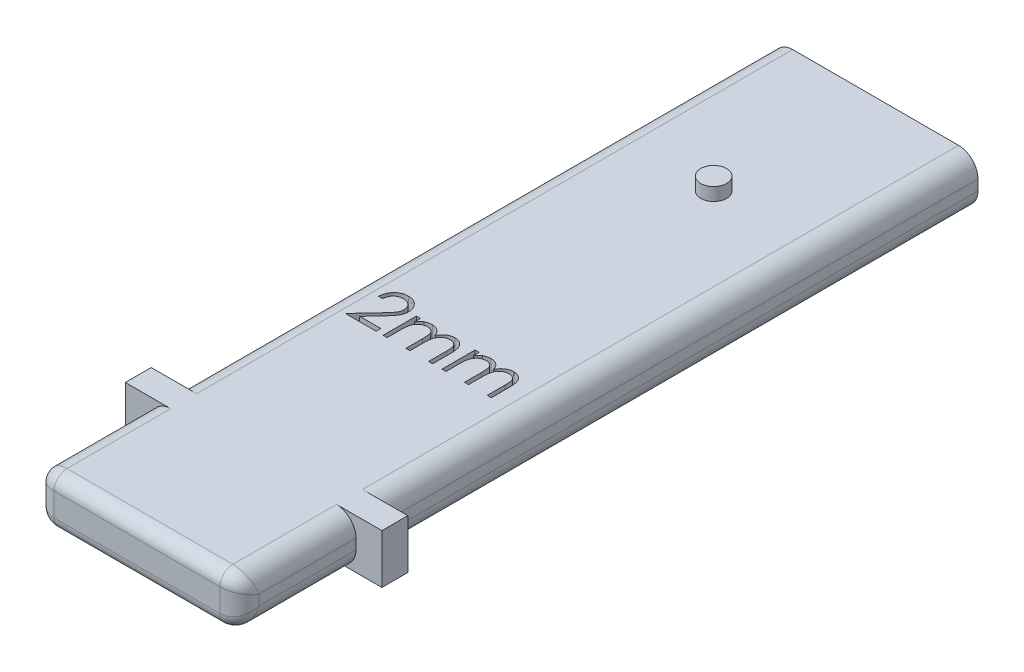
SolidWorks part; units mm, degrees
ref_plane "Front Plane" through (0, 0, 0) normal (0, 0, 1) x (1, 0, 0)
ref_plane "Top Plane" through (0, 0, 0) normal (0, 1, 0) x (1, 0, 0)
ref_plane "Right Plane" through (0, 0, 0) normal (1, 0, 0) x (0, 0, -1)
sketch "Sketch2" plane through (0, 0, 0) normal (0, 1, 0) x (1, 0, 0)
  line L1 (0, 0) -> (15.8, 0)
  line L2 (0, 0) -> (0, 57)
  line L3 (0, 57) -> (15.8, 57)
  line L4 (15.8, 0) -> (15.8, 57)
  dimension "D1" = 57
  dimension "D2" = 15.8
extrude "Boss-Extrude1" add sketch "Sketch2" along normal blind 3.8
fillet "Fillet3" radius 1 2 edges at (7.9, 0, 0) (7.9, 3.8, 0)
sketch "Sketch5" plane through (0, 3.8, 0) normal (0, 1, 0) x (1, 0, 0)
  line L0 (15.8, 57) -> (0, 57) construction
  circle A0 centre (7.9, 44.5) radius 1
  point P4 (7.9, 57)
  dimension "D1" = 2
  dimension "D2" = 12.5
extrude "Boss-Extrude4" add sketch "Sketch5" along normal blind 1
sketch "Sketch6" plane through (15.8, 0, 0) normal (1, 0, 0) x (0, 0, -1)
  line L0 (9, 3.8) -> (9, 0)
  line L1 (1, 3.8) -> (57, 3.8) construction
  line L2 (1, 0) -> (57, 0) construction
  line L3 (9, 0) -> (11, 0)
  line L4 (11, 0) -> (11, 3.8)
  line L5 (11, 3.8) -> (9, 3.8)
  line L6 (0, 2.8) -> (0, 1) construction
  dimension "D1" = 9
  dimension "D2" = 2
extrude "Boss-Extrude5" add sketch "Sketch6" along normal blind 2
sketch "Sketch7" plane through (0, 0, 0) normal (-1, 0, 0) x (0, 0, 1)
  line L0 (-57, 0) -> (-1, 0) construction
  line L1 (-9, 0) -> (-11, 0)
  line L2 (-9, 0) -> (-9, 3.8)
  line L3 (-9, 3.8) -> (-11, 3.8)
  line L4 (-11, 0) -> (-11, 3.8)
  line L5 (-57, 3.8) -> (-1, 3.8) construction
  line L6 (0, 2.8) -> (0, 1) construction
  dimension "D1" = 9
  dimension "D2" = 2
extrude "Boss-Extrude6" add sketch "Sketch7" along normal blind 2
fillet "Fillet4" radius 1.5 14 edges at (0, 0.2929, -0.2929) (0, 1.9, 0) (0, 3.5071, -0.2929) (15.8, 0.2929, -0.2929) (15.8, 1.9, 0) (15.8, 3.5071, -0.2929) (0, 0, -34) (0, 0, -5) (0, 3.8, -5) (0, 3.8, -34) (15.8, 0, -34) (15.8, 3.8, -34) (15.8, 0, -5) (15.8, 3.8, -5)
sketch "Sketch9" plane through (0, 3.8, 0) normal (0, 1, 0) x (1, 0, 0)
  text T0 "2mm"
extrude "Cut-Extrude1" cut sketch "Sketch9" against normal blind 5
